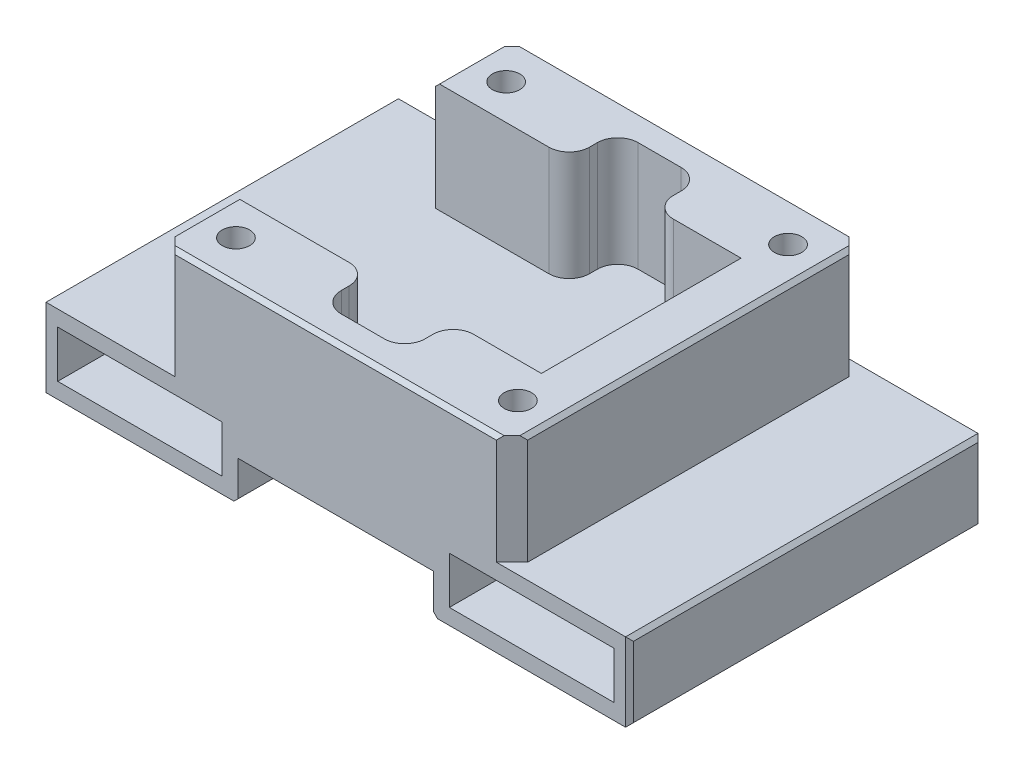
SolidWorks part; units mm, degrees
ref_plane "Front Plane" through (0, 0, 0) normal (0, 0, 1) x (1, 0, 0)
ref_plane "Top Plane" through (0, 0, 0) normal (0, 1, 0) x (1, 0, 0)
ref_plane "Right Plane" through (0, 0, 0) normal (1, 0, 0) x (0, 0, -1)
sketch "Sketch1" plane through (0, 0, 0) normal (0, 1, 0) x (1, 0, 0)
  line L1 (-22.5, -22.5) -> (22.5, -22.5)
  line L2 (-22.5, -22.5) -> (-22.5, 22.5)
  line L3 (-22.5, 22.5) -> (22.5, 22.5)
  line L4 (22.5, -22.5) -> (22.5, 22.5)
  line L5 (-22.5, -22.5) -> (22.5, 22.5) construction
  line L6 (-22.5, 22.5) -> (22.5, -22.5) construction
  point P0 (0, 0)
  dimension "D1" = 45
  dimension "D2" = 45
extrude "Boss-Extrude1" add sketch "Sketch1" along normal blind 14
sketch "Sketch3" plane through (0, 14, 0) normal (0, 1, 0) x (1, 0, 0)
  line L0 (-22.5, 12.75) -> (-8.05, 12.75)
  line L2 (-22.5, -12.75) -> (-22.5, 12.75)
  line L4 (16.5, -12.75) -> (16.5, 12.75)
  line L6 (-5.45, 15.35) -> (-5.45, 16.35)
  line L8 (5.25, 15.35) -> (5.25, 16.35)
  line L13 (-2.85, 18.95) -> (2.65, 18.95)
  line L14 (7.85, 12.75) -> (16.5, 12.75)
  line L15 (22.5, -22.5) -> (22.5, 22.5) construction
  line L16 (-22.5, -12.75) -> (-8.05, -12.75)
  line L17 (-5.45, -15.35) -> (-5.45, -16.35)
  line L18 (-2.85, -18.95) -> (2.65, -18.95)
  line L19 (5.25, -16.35) -> (5.25, -15.35)
  line L20 (7.85, -12.75) -> (16.5, -12.75)
  line L21 (-22.5, 22.5) -> (-22.5, -22.5) construction
  arc A0 (2.65, -18.95) -> (5.25, -16.35) centre (2.65, -16.35) ccw
  arc A1 (-5.45, -16.35) -> (-2.85, -18.95) centre (-2.85, -16.35) ccw
  arc A2 (5.25, -15.35) -> (7.85, -12.75) centre (7.85, -15.35) cw
  arc A3 (-8.05, -12.75) -> (-5.45, -15.35) centre (-8.05, -15.35) cw
  arc A4 (7.85, 12.75) -> (5.25, 15.35) centre (7.85, 15.35) cw
  arc A5 (-8.05, 12.75) -> (-5.45, 15.35) centre (-8.05, 15.35) ccw
  arc A6 (2.65, 18.95) -> (5.25, 16.35) centre (2.65, 16.35) cw
  arc A7 (-5.45, 16.35) -> (-2.85, 18.95) centre (-2.85, 16.35) cw
  point P0 (0, 0)
  point P7 (-22.5, 0)
  point P46 (-0.1, 18.95)
  dimension "D7" = 2.6
  dimension "D1" = 6.2
  dimension "D2" = 25.5
  dimension "D3" = 5.5
  dimension "D5" = 11.25
  dimension "D6" = 6
extrude "Cut-Extrude1" cut sketch "Sketch3" against normal through all
chamfer "Chamfer1" distance 0.5 angle 45 5 edges at (-22.5, 14, -17.625) (-22.5, 14, 17.625) (0, 14, 22.5) (22.5, 14, 0) (0, 14, -22.5)
chamfer "Chamfer2" distance 2 angle 45 4 edges at (-22.5, 6.75, 22.5) (22.5, 6.75, 22.5) (22.5, 6.75, -22.5) (-22.5, 6.75, -22.5)
sketch "Sketch4" plane through (0, 14, 0) normal (0, 1, 0) x (1, 0, 0)
  line L0 (-18, 12.75) -> (-18, 22) construction
  line L1 (21, 22) -> (-21, 22) construction
  line L3 (-22, 17.25) -> (-18, 17.25) construction
  line L4 (-22, 21) -> (-22, 12.75) construction
  line L5 (22, 17.25) -> (18, 17.25) construction
  line L6 (22, -21) -> (22, 21) construction
  line L7 (18, 17.25) -> (18, 22) construction
  line L8 (-22, -17.25) -> (-18, -17.25) construction
  line L9 (18, -22) -> (18, -17.25) construction
  line L10 (-21, -22) -> (21, -22) construction
  line L11 (18, -17.25) -> (22, -17.25) construction
  line L12 (-22, -12.75) -> (-22, -21) construction
  line L13 (-8.05, 12.75) -> (-22, 12.75) construction
  circle A0 centre (-18, 17.25) radius 1.75
  circle A2 centre (18, 17.25) radius 1.75
  circle A3 centre (18, -17.25) radius 1.75
  circle A4 centre (-18, -17.25) radius 1.75
extrude "Cut-Extrude2" cut sketch "Sketch4" against normal through all
sketch "Sketch5" plane through (0, 0, 0) normal (0, -1, 0) x (1, 0, 0)
  line L1 (-37.5, 22.5) -> (37.5, 22.5)
  line L2 (-37.5, 22.5) -> (-37.5, -22.5)
  line L3 (-37.5, -22.5) -> (37.5, -22.5)
  line L4 (37.5, 22.5) -> (37.5, -22.5)
  line L5 (-37.5, 22.5) -> (37.5, -22.5) construction
  line L6 (-37.5, -22.5) -> (37.5, 22.5) construction
  line L7 (-37.5, 22.5) -> (-12.5, 22.5)
  line L8 (-37.5, 22.5) -> (-37.5, -22.5)
  line L9 (-37.5, -22.5) -> (-12.5, -22.5)
  line L10 (-12.5, 22.5) -> (-12.5, -22.5)
  line L11 (37.5, 22.5) -> (12.5, 22.5)
  line L12 (37.5, 22.5) -> (37.5, -22.5)
  line L13 (37.5, -22.5) -> (12.5, -22.5)
  line L14 (12.5, 22.5) -> (12.5, -22.5)
  point P0 (0, 0)
  circle M5 centre (-18, 17.25) radius 1.75
  circle M6 centre (18, 17.25) radius 1.75
  circle M7 centre (18, -17.25) radius 1.75
  circle M8 centre (-18, -17.25) radius 1.75
  line M9 (20.5, 22.5) -> (-20.5, 22.5)
  line M10 (-20.5, 22.5) -> (-22.5, 20.5)
  line M11 (-22.5, 20.5) -> (-22.5, 12.75)
  line M12 (-22.5, 12.75) -> (-8.05, 12.75)
  arc M13 (-8.05, 12.75) -> (-5.45, 15.35) centre (-8.05, 15.35) ccw
  line M14 (-5.45, 15.35) -> (-5.45, 16.35)
  arc M15 (-5.45, 16.35) -> (-2.85, 18.95) centre (-2.85, 16.35) cw
  line M16 (-2.85, 18.95) -> (2.65, 18.95)
  arc M17 (2.65, 18.95) -> (5.25, 16.35) centre (2.65, 16.35) cw
  line M18 (5.25, 16.35) -> (5.25, 15.35)
  arc M19 (5.25, 15.35) -> (7.85, 12.75) centre (7.85, 15.35) ccw
  line M20 (7.85, 12.75) -> (16.5, 12.75)
  line M21 (16.5, 12.75) -> (16.5, -12.75)
  line M22 (16.5, -12.75) -> (7.85, -12.75)
  arc M23 (7.85, -12.75) -> (5.25, -15.35) centre (7.85, -15.35) ccw
  line M24 (5.25, -15.35) -> (5.25, -16.35)
  arc M25 (5.25, -16.35) -> (2.65, -18.95) centre (2.65, -16.35) cw
  line M26 (2.65, -18.95) -> (-2.85, -18.95)
  arc M27 (-2.85, -18.95) -> (-5.45, -16.35) centre (-2.85, -16.35) cw
  line M28 (-5.45, -16.35) -> (-5.45, -15.35)
  arc M29 (-5.45, -15.35) -> (-8.05, -12.75) centre (-8.05, -15.35) ccw
  line M30 (-8.05, -12.75) -> (-22.5, -12.75)
  line M31 (-22.5, -12.75) -> (-22.5, -20.5)
  line M32 (-22.5, -20.5) -> (-20.5, -22.5)
  line M33 (-20.5, -22.5) -> (20.5, -22.5)
  line M34 (20.5, -22.5) -> (22.5, -20.5)
  line M35 (22.5, -20.5) -> (22.5, 20.5)
  line M36 (22.5, 20.5) -> (20.5, 22.5)
  dimension "D1" = 75
  dimension "D2" = 45
  dimension "D3" = 25
  dimension "D4" = 25
extrude "Boss-Extrude4" add sketch "Sketch5" along normal blind 5 contours L10 L1 L2 L3 M12 M11 M10 M32 M31 M30 | L14 L10 M20 M19 M18 M17 M16 M15 M14 M13 M12 M30 M29 M28 M27 M26 M25 M24 M23 M22 | L14 L1 L10 M12 M13 M14 M15 M16 M17 M18 M19 M20 | L10 L1 M10 M11 M12 M5 | L14 M9 M20 M21 M22 M33 M34 M35 M36 M6 M7 | L4 L1 L3 M36 M35 M34 | L14 L10 L3 M22 M23 M24 M25 M26 M27 M28 M29 M30 | L10 M30 M31 M32 M33 M8 | L14 M20 M22 M21 | M6 | M5 | M8 | M7 region at (-26.5523, 0, 0) region at (-16.5, 0, 22.3603) region at (0, 0, 22.2317) region at (-21.4012, 0, -21.4012) region at (18.3592, 0, 0) region at (-0.0172, 0, 0) region at (-12.2317, 0, -17.625) region at (29.9519, 0, 0) region at (14.5, 0, 0) region at (-18, 0, 17.25) region at (18, 0, 17.25) region at (18, 0, -17.25) region at (-18, 0, -17.25)
extrude "Boss-Extrude5" add sketch "Sketch5<3>" along normal blind 10 contours L10 L1 M10 M11 M12 M5 | L10 L1 L2 L3 M12 M11 M10 M32 M31 M30 | L10 M30 M31 M32 M33 M8 | M5 | M8 | L14 M9 M20 M21 M22 M33 M34 M35 M36 M6 M7 | L4 L1 L3 M36 M35 M34 | L14 M20 M22 M21 | M6 | M7 region at (-26.5523, 0, 0) region at (-16.5, 0, 22.3603) region at (-21.4012, 0, -21.4012) region at (18.3592, 0, 0) region at (29.9519, 0, 0) region at (14.5, 0, 0) region at (-18, 0, 17.25) region at (18, 0, 17.25) region at (18, 0, -17.25) region at (-18, 0, -17.25)
sketch "Sketch5<3>" plane through (0, 0, 0) normal (0, -1, 0) x (1, 0, 0) same geometry as "Sketch5"
sketch "Sketch10" plane through (0, 0, -22.5) normal (0, 0, -1) x (-1, 0, 0)
  line L0 (-37.5, -10) -> (-37.5, 0) construction
  line L1 (-35.5, -2) -> (-14.5, -2)
  line L2 (-35.5, -2) -> (-35.5, -8)
  line L3 (-35.5, -8) -> (-14.5, -8)
  line L4 (-14.5, -2) -> (-14.5, -8)
  line L5 (-12.5, -10) -> (-37.5, -10) construction
  line L6 (-20.5, 0) -> (-37.5, 0) construction
  line L7 (-12.5, -10) -> (-12.5, -5) construction
  line L8 (37.5, -10) -> (37.5, 0) construction
  line L9 (14.5, -8) -> (35.5, -8)
  line L10 (14.5, -8) -> (14.5, -2)
  line L11 (14.5, -2) -> (35.5, -2)
  line L12 (35.5, -8) -> (35.5, -2)
  line L13 (12.5, -10) -> (12.5, -5) construction
  line L14 (37.5, 0) -> (20.5, 0) construction
  line L15 (37.5, -10) -> (12.5, -10) construction
  dimension "D1" = 2
  dimension "D2" = 2
  dimension "D3" = 2
  dimension "D4" = 2
  dimension "D5" = 2
  dimension "D6" = 2
  dimension "D7" = 2
  dimension "D8" = 2
extrude "Cut-Extrude3" cut sketch "Sketch10" against normal blind 50
chamfer "Chamfer5" distance 0.5 angle 45 10 edges at (-37.5, -5, 22.5) (-37.5, 0, 0) (-37.5, -5, -22.5) (-37.5, -10, 0) (-12.5, -10, 0) (12.5, -10, 0) (37.5, -5, -22.5) (37.5, -10, 0) (37.5, -5, 22.5) (37.5, 0, 0)
